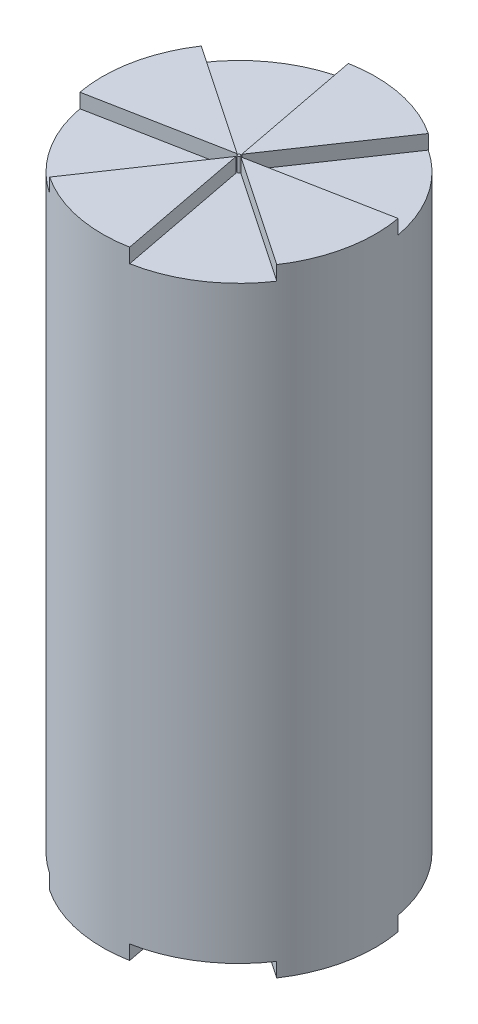
SolidWorks part; units mm, degrees
material "Nylon 101"
ref_plane "Front" through (0, 0, 0) normal (0, 0, 1) x (1, 0, 0)
ref_plane "Top" through (0, 0, 0) normal (0, 1, 0) x (1, 0, 0)
ref_plane "Right" through (0, 0, 0) normal (1, 0, 0) x (0, 0, -1)
sketch "Sketch1" plane through (0, 0, 0) normal (0, 1, 0) x (1, 0, 0)
  circle A0 centre (0, 0) radius 24.13
  dimension "D1" = 48.26
extrude "Boss-Extrude1" add sketch "Sketch1" along normal blind 109.22
sketch "Sketch2" plane through (0, 109.22, 0) normal (0, 1, 0) x (1, 0, 0)
  line L6 (-13.3984, -20.0684) -> (0.0237, -0.2529)
  line L7 (-0.2231, 0.1215) -> (-23.7256, -4.3994)
  arc A6 (-13.3984, -20.0684) -> (-23.7256, -4.3994) centre (0, 0) cw
  arc A7 (0.0237, -0.2529) -> (-0.2231, 0.1215) centre (0, 0) cw
  circle A8 centre (0, 0) radius 24.13 construction
  dimension "D1" = 45
  dimension "D2" = 0.254
extrude "Cut-Extrude7" cut sketch "Sketch2" against normal blind 2.54
pattern_circular "CirPattern2" count 4 over 360 about axis through (0, 109.22, 0) along (0, 1, 0) of "Cut-Extrude7"
ref_plane "Plane1" through (0, 54.61, 0) normal (0, 1, 0) x (1, 0, 0)
mirror "Mirror1" about plane through (0, 54.61, 0) normal (0, 1, 0) of "CirPattern2"
